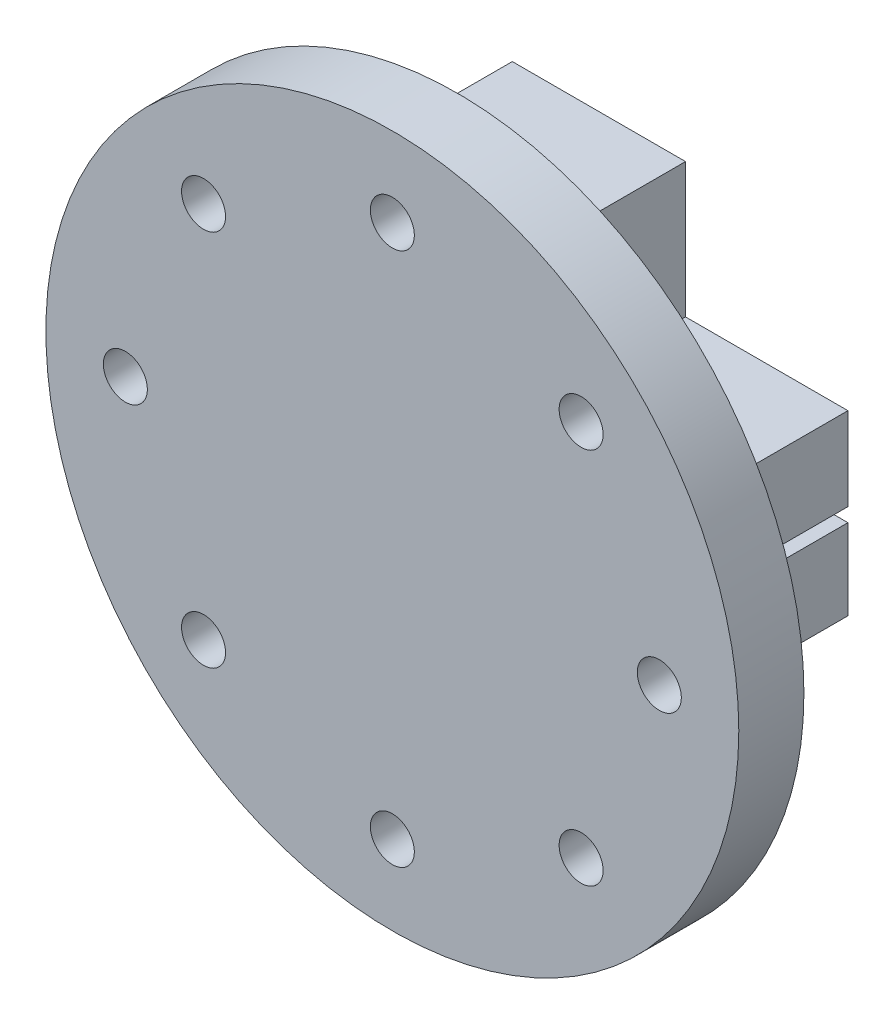
SolidWorks part; units mm, degrees
ref_plane "Front Plane" through (0, 0, 0) normal (0, 0, 1) x (1, 0, 0)
ref_plane "Top Plane" through (0, 0, 0) normal (0, 1, 0) x (1, 0, 0)
ref_plane "Right Plane" through (0, 0, 0) normal (1, 0, 0) x (0, 0, -1)
sketch "草图1" plane through (0, 0, 0) normal (0, 0, 1) x (1, 0, 0)
  line L0 (0, 0) -> (6, 0)
  line L1 (6, 0) -> (7, 0)
  line L3 (0, 0) -> (0, -2)
  line L5 (7, -2) -> (7, 0)
  line L6 (0, 0) -> (0, 6)
  line L8 (0, 2) -> (0, 0)
  line L9 (0, 0) -> (7, 0)
  line L10 (7, 2) -> (7, 0)
  line L11 (0, 0) -> (-6, 0)
  line L12 (-6, 6) -> (6, -6) construction
  line L13 (6, 6) -> (-6, -6) construction
  line L14 (-6, 6) -> (-7.4142, 7.4142) construction
  line L16 (-6, 6) -> (-6, -6)
  line L17 (-6, 6) -> (6, 6)
  line L18 (-6, 6) -> (-6, -6)
  line L19 (-6, -6) -> (6, -6)
  line L20 (6, 6) -> (6, -6)
  line L23 (-7.4142, 7.4142) -> (-7.4142, -7.4142) construction
  line L24 (0, 2) -> (6, 2)
  line L25 (-7.4142, 7.4142) -> (22.5858, 7.4142)
  line L26 (-7.4142, 7.4142) -> (-7.4142, -7.4142)
  line L27 (-7.4142, -7.4142) -> (22.5858, -7.4142)
  line L28 (22.5858, 7.4142) -> (22.5858, -7.4142)
  line L29 (6, 2) -> (6, -2)
  line L30 (6, -2) -> (0, -2)
  line L32 (6, 2) -> (7, 2)
  line L33 (6, 2) -> (6, -2)
  line L34 (6, -2) -> (7, -2)
  line L35 (7, 2) -> (7, -2)
  line L36 (0, 2) -> (6, 2)
  line L37 (0, 2) -> (0, -2)
  line L38 (0, -2) -> (6, -2)
  line L39 (6, 2) -> (6, -2)
  line L41 (6, 3) -> (6, -3)
  line L42 (6, 3) -> (18, 3)
  line L43 (6, 3) -> (6, -3)
  line L44 (6, -3) -> (18, -3)
  line L45 (18, 3) -> (18, -3)
  line L47 (7, 2) -> (7, -2)
  line L49 (18, 2) -> (18, -2)
  line L50 (18, -1) -> (7, -1)
  line L51 (18, -1) -> (18, 1)
  line L52 (18, 1) -> (7, 1)
  line L53 (7, -1) -> (7, 1)
  line L54 (18, 3) -> (20.8501, 3)
  line L55 (18, 3) -> (18, 1)
  line L56 (18, 1) -> (20.8501, 1)
  line L57 (20.8501, 3) -> (20.8501, 1)
  line L62 (18, -1) -> (20.8501, -1)
  line L63 (18, -1) -> (18, -3)
  line L64 (18, -3) -> (20.8501, -3)
  line L65 (20.8501, -1) -> (20.8501, -3)
  line L66 (7, 2) -> (7.7, 2)
  line L67 (7, 2) -> (7, 1)
  line L68 (7, 1) -> (7.7, 1)
  line L69 (7.7, 2) -> (7.7, 1)
  line L70 (7, -2) -> (7.7, -2)
  line L71 (7, -2) -> (7, -1)
  line L72 (7, -1) -> (7.7, -1)
  line L73 (7.7, -2) -> (7.7, -1)
  circle A0 centre (0, 0) radius 6
  circle A2 centre (0, 0) radius 10.4853
  point P20 (6, 2)
  point P21 (6, -2)
  point P22 (6, 3)
  point P25 (6, -3)
  point P30 (10.2928, 2)
  point P31 (10.2928, -2)
  point P32 (18, 1)
  point P33 (18, -1)
  point P34 (18, 1)
  dimension "D1" = 12
  dimension "D2" = 6
  dimension "D3" = 2
  dimension "D4" = 12
  dimension "D5" = 12
  dimension "D6" = 2
  dimension "D7" = 30
  dimension "D8" = 14.8284
  dimension "D9" = 6
  dimension "D10" = 0.7
  dimension "D11" = 0.7
extrude "凸台-拉伸2" add sketch "草图1" along normal blind 25.5 contours L25 L28 L27 L26
extrude "切除-拉伸9" cut sketch "草图1<11>" along normal blind 46 contours L11 A0 L3 region at (-0.7742, -2.9557, 0)
sketch "草图1<11>" plane through (0, 0, 0) normal (0, 0, 1) x (1, 0, 0) same geometry as "草图1"
extrude "切除-拉伸10" cut sketch "草图1<12>" along normal blind 30 contours L6 A0 L11 region at (-2.5465, 2.5465, 0)
sketch "草图1<12>" plane through (0, 0, 0) normal (0, 0, 1) x (1, 0, 0) same geometry as "草图1"
extrude "切除-拉伸11" cut sketch "草图1<13>" along normal blind 31 contours L0 A0 region at (2.9444, 0.9903, 0)
sketch "草图1<13>" plane through (0, 0, 0) normal (0, 0, 1) x (1, 0, 0) same geometry as "草图1"
extrude "切除-拉伸12" cut sketch "草图1<14>" along normal blind 40 contours A0 L0 L3 region at (2.9444, -0.9903, 0)
sketch "草图1<14>" plane through (0, 0, 0) normal (0, 0, 1) x (1, 0, 0) same geometry as "草图1"
extrude "切除-拉伸13" cut sketch "草图1<15>" along normal blind 46 contours A0 L6 region at (2.2626, 3.6569, 0)
sketch "草图1<15>" plane through (0, 0, 0) normal (0, 0, 1) x (1, 0, 0) same geometry as "草图1"
extrude "切除-拉伸17" cut sketch "草图1<19>" along normal blind 97 contours A0 L20 L36 | L32 L20 L1 L10 | L20 L34 L5 L1 | A0 L30 L20 region at (6.5, 1, 0) region at (5.8976, 1.5029, 0) region at (6.5, -1, 0) region at (5.8976, -1.5029, 0)
sketch "草图1<19>" plane through (0, 0, 0) normal (0, 0, 1) x (1, 0, 0) same geometry as "草图1"
extrude "切除-拉伸18" cut sketch "草图1<20>" along normal blind 285 contours A2 L49 L27 L28 L25 region at (9.1874, 5.4796, 0)
sketch "草图1<20>" plane through (0, 0, 0) normal (0, 0, 1) x (1, 0, 0) same geometry as "草图1"
sketch "草图12" plane through (0, 0, 25.5) normal (0, 0, 1) x (1, 0, 0)
  line L0 (0, 0) -> (0, 50)
  line L5 (0, 0) -> (-35.3553, 35.3553)
  line L6 (-35.3553, 35.3553) -> (35.3553, -35.3553)
  line L7 (35.3553, 0) -> (41.7053, 0)
  line L8 (-35.3553, 35.3553) -> (35.3553, 35.3553)
  line L9 (-35.3553, 35.3553) -> (-35.3553, -35.3553)
  line L10 (-35.3553, -35.3553) -> (35.3553, -35.3553)
  line L11 (35.3553, 35.3553) -> (35.3553, -35.3553)
  circle A0 centre (0, 0) radius 50
  circle A9 centre (38.5303, 0) radius 3.175
  circle A10 centre (27.2451, -27.2451) radius 3.175
  circle A11 centre (0, -38.5303) radius 3.175
  circle A12 centre (-27.2451, -27.2451) radius 3.175
  circle A13 centre (-38.5303, 0) radius 3.175
  circle A14 centre (-27.2451, 27.2451) radius 3.175
  circle A15 centre (0, 38.5303) radius 3.175
  circle A16 centre (27.2451, 27.2451) radius 3.175
  point P11 (-25, 25)
  point P12 (-25, -25)
  point P13 (24.6474, -24.6474)
  point P31 (0, 0)
  point P33 (0, 0)
  dimension "D1" = 6.35
  dimension "D2" = 8
extrude "凸台-拉伸7" add sketch "草图12" along normal blind 9.398 contours A0
sketch "草图16" plane through (0, 0, 0) normal (0, 0, -1) x (-1, 0, 0)
  line L0 (-7, -2) -> (-7, 2) construction
  line L1 (-18, 1) -> (-7, 1) construction
  line L2 (-18, 1) -> (-18, -1) construction
  line L3 (-18, -1) -> (-7, -1) construction
  line L4 (-7, 1) -> (-7, -1) construction
  line L5 (-18, 1) -> (-18, -1)
  line L6 (-18, -1) -> (-7, -1)
  line L7 (-7, -1) -> (-7, 1)
  line L8 (-7, 1) -> (-18, 1)
extrude "切除-拉伸25" cut sketch "草图16" against normal blind 25.5 contours L8 L5 L6 L7
extrude "切除-拉伸27" cut sketch "草图12<5>" along normal blind 63 contours A16 | A14 | A13 | A12 | A11 | A10 | A9 | A15 region at (27.2451, 27.2451, 25.5)
sketch "草图12<5>" plane through (0, 0, 25.5) normal (0, 0, 1) x (1, 0, 0) same geometry as "草图12"
sketch "草图20" plane through (0, 0, 0) normal (0, 0, -1) x (-1, 0, 0)
  line L1 (-7.4142, 7.4142) -> (17.5858, 7.4142)
  line L2 (-7.4142, 7.4142) -> (-7.4142, 32.4142)
  line L3 (-7.4142, 32.4142) -> (17.5858, 32.4142)
  line L4 (17.5858, 7.4142) -> (17.5858, 32.4142)
  line L5 (7.4142, -7.4142) -> (17.5858, -7.4142)
  line L6 (7.4142, -7.4142) -> (7.4142, 7.4142)
  line L7 (7.4142, 7.4142) -> (17.5858, 7.4142)
  line L8 (17.5858, -7.4142) -> (17.5858, 7.4142)
  line L10 (17.5858, -7.4142) -> (17.5858, -32.4142)
  line L21 (-20.8501, 3) -> (-7.4142, 3)
  line L22 (-20.8501, 3) -> (-20.8501, 23)
  line L23 (-20.8501, 23) -> (-7.4142, 23)
  line L24 (-7.4142, 3) -> (-7.4142, 23)
  line L25 (-20.8501, 23) -> (-30.8501, 23)
  line L26 (-20.8501, 23) -> (-20.8501, 3)
  line L27 (-20.8501, 3) -> (-30.8501, 3)
  line L28 (-30.8501, 23) -> (-30.8501, 3)
  line L29 (-20.8501, -3) -> (-7.4142, -3)
  line L30 (-20.8501, -3) -> (-20.8501, -22.6415)
  line L31 (-20.8501, -22.6415) -> (-7.4142, -22.6415)
  line L32 (-7.4142, -3) -> (-7.4142, -22.6415)
  line L33 (-20.8501, -22.6415) -> (-30.8501, -22.6415)
  line L34 (-20.8501, -22.6415) -> (-20.8501, -3)
  line L35 (-20.8501, -3) -> (-30.8501, -3)
  line L36 (-30.8501, -22.6415) -> (-30.8501, -3)
  line L37 (-7.4142, -7.4142) -> (17.5858, -7.4142)
  line L38 (-7.4142, -7.4142) -> (-7.4142, -32.4142)
  line L39 (-7.4142, -32.4142) -> (17.5858, -32.4142)
  line L40 (17.5858, -7.4142) -> (17.5858, -32.4142)
  line L41 (-20.8501, 1) -> (-30.8501, 1)
  line L42 (-20.8501, 1) -> (-20.8501, 3)
  line L43 (-20.8501, 3) -> (-30.8501, 3)
  line L44 (-30.8501, 1) -> (-30.8501, 3)
  line L45 (-20.8501, -1) -> (-30.8501, -1)
  line L46 (-20.8501, -1) -> (-20.8501, -3)
  line L47 (-20.8501, -3) -> (-30.8501, -3)
  line L48 (-30.8501, -1) -> (-30.8501, -3)
  line M21 (-20.8501, -1) -> (-20.8501, -3)
  line M22 (-20.8501, -3) -> (-10.0469, -3)
  arc M23 (-10.0469, -3) -> (-7.4142, -7.4142) centre (0, 0) ccw
  line M24 (-7.4142, -7.4142) -> (7.4142, -7.4142)
  line M25 (7.4142, -7.4142) -> (7.4142, 7.4142)
  line M26 (7.4142, 7.4142) -> (-7.4142, 7.4142)
  arc M27 (-7.4142, 7.4142) -> (-10.0469, 3) centre (0, 0) ccw
  line M28 (-10.0469, 3) -> (-20.8501, 3)
  line M29 (-20.8501, 3) -> (-20.8501, 1)
  dimension "D1" = 25
  dimension "D2" = 25
  dimension "D3" = 25
  dimension "D4" = 20
  dimension "D5" = 10
  dimension "D6" = 10
extrude "凸台-拉伸9" add sketch "草图20" against normal blind 26 contours L1 L4 L3 L2 M26 | L23 L22 L2 M28 M27 | L25 L28 L27 L22 | L36 L33 L30 L35 | L32 L30 L31 M23 M22 | L38 L39 L10 L5 L32 M24 | L5 L8 L1 M25 | L32 L29 M23 | L21 L24 M27 region at (-5.0858, 19.9142, 0) region at (14.284, 13.2217, 0) region at (8.3791, 4.5989, 0) region at (-12.5, 0, 0) region at (-5.0858, -19.9142, 0) region at (25.8501, 13, 0) region at (8.3791, -4.5989, 0) region at (14.2868, -13.0418, 0) region at (25.8501, -12.8207, 0)
extrude "凸台-拉伸10" add sketch "草图20<8>" against normal blind 26 contours L44 L41 L27 M29 | L45 L48 L35 M21 region at (25.8501, 2, 0) region at (25.8501, -2, 0)
sketch "草图20<8>" plane through (0, 0, 0) normal (0, 0, -1) x (-1, 0, 0) same geometry as "草图20"
sketch "草图21" plane through (0, -22.6415, 0) normal (0, -1, 0) x (1, 0, 0)
  line L0 (30.8501, 25.5) -> (7.4142, 0) construction
  line L1 (7.4142, 25.5) -> (30.8501, 0) construction
  circle A0 centre (19.1322, 12.75) radius 3.175
  point P8 (19.1322, 12.75)
  point P9 (9.7024, 20.568)
  dimension "D1" = 6.35
extrude "切除-拉伸28" cut sketch "草图21" against normal blind 54
sketch "草图22" plane through (0, 0, 0) normal (0, 0, -1) x (-1, 0, 0)
  line L0 (-30.8501, -1) -> (-30.8501, -22.6415) construction
  line L1 (-30.8501, -12.6415) -> (-7.4142, -12.6415)
  line L2 (-30.8501, -12.6415) -> (-30.8501, -22.6415)
  line L3 (-30.8501, -22.6415) -> (-7.4142, -22.6415)
  line L4 (-7.4142, -12.6415) -> (-7.4142, -22.6415)
  line L6 (-30.8501, 23) -> (-7.4142, 23)
  line L7 (-30.8501, 23) -> (-30.8501, 13)
  line L8 (-30.8501, 13) -> (-7.4142, 13)
  line L9 (-7.4142, 23) -> (-7.4142, 13)
  dimension "D1" = 10
  dimension "D2" = 10
extrude "切除-拉伸31" cut sketch "草图22" against normal blind 25.5
extrude "切除-拉伸32" cut sketch "草图1<26>" along normal blind 25.5 contours L69 L66 L10 L52 | L70 L73 L50 L5 region at (7.35, -1.5, 0) region at (7.35, 1.5, 0)
sketch "草图1<26>" plane through (0, 0, 0) normal (0, 0, 1) x (1, 0, 0) same geometry as "草图1"
